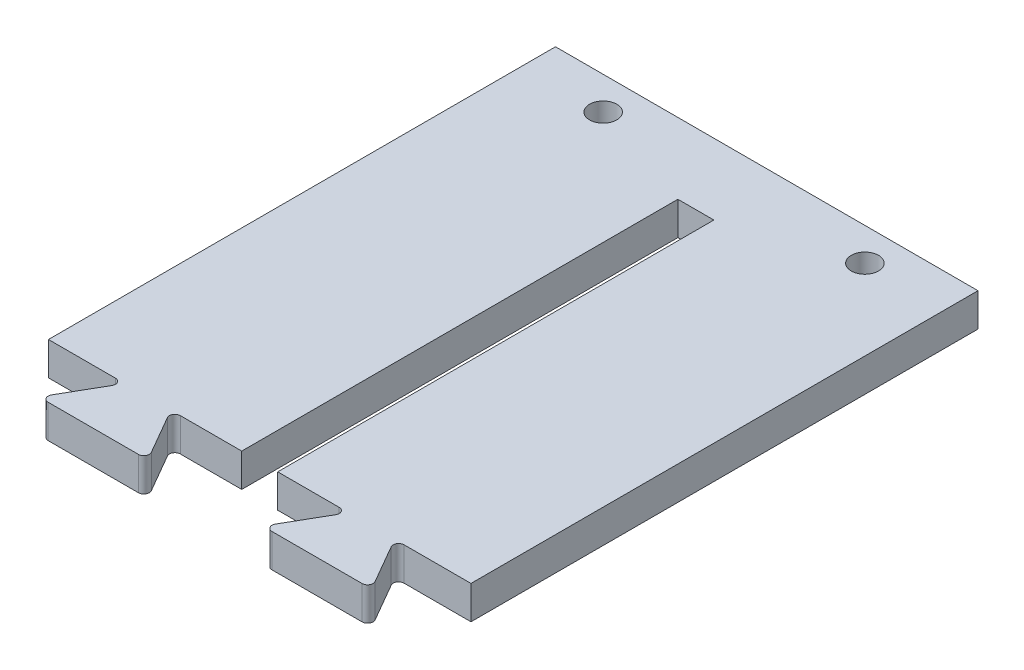
SolidWorks part; units mm, degrees
ref_plane "Front Plane" through (0, 0, 0) normal (0, 0, 1) x (1, 0, 0)
ref_plane "Top Plane" through (0, 0, 0) normal (0, 1, 0) x (1, 0, 0)
ref_plane "Right Plane" through (0, 0, 0) normal (1, 0, 0) x (0, 0, -1)
sketch "Sketch1" plane through (0, 0, 0) normal (0, 1, 0) x (1, 0, 0)
  line L0 (-19.375, 0) -> (-19.375, 46.5)
  line L1 (-19.375, 46.5) -> (19.375, 46.5)
  line L2 (19.375, 46.5) -> (19.375, 0)
  line L3 (19.375, 0) -> (12.375, 0)
  line L4 (12.375, 0) -> (15.2618, -5)
  line L5 (15.2618, -5) -> (5.2618, -5)
  line L6 (5.2618, -5) -> (8.1485, 0)
  line L7 (8.1485, 0) -> (-8.1485, 0)
  line L8 (-8.1485, 0) -> (-5.2618, -5)
  line L9 (-5.2618, -5) -> (-15.2618, -5)
  line L10 (-15.2618, -5) -> (-12.375, 0)
  line L11 (-12.375, 0) -> (-19.375, 0)
  point P13 (0, 0)
  dimension "D1" = 46.5
  dimension "D2" = 38.75
  dimension "D3" = 10
  dimension "D4" = 10
  dimension "D5" = 60
  dimension "D6" = 60
  dimension "D7" = 7
  dimension "D8" = 7
  dimension "D9" = 5
  dimension "D10" = 5
extrude "Boss-Extrude1" add sketch "Sketch1" along normal blind 3.05
fillet "Fillet1" radius 0.5 8 edges at (12.375, 1.525, 0) (15.2618, 1.525, 5) (5.2618, 1.525, 5) (8.1485, 1.525, 0) (-8.1485, 1.525, 0) (-5.2618, 1.525, 5) (-15.2618, 1.525, 5) (-12.375, 1.525, 0)
sketch "Sketch3" plane through (0, 3.05, 0) normal (0, 1, 0) x (1, 0, 0)
  line L0 (0, 40) -> (0, 0) construction
  line L2 (19.375, 46.5) -> (-19.375, 46.5) construction
  line L3 (-1.65, 40) -> (1.65, 40)
  line L4 (-1.65, 40) -> (-1.65, 0)
  line L5 (-1.65, 0) -> (1.65, 0)
  line L6 (1.65, 40) -> (1.65, 0)
  line L8 (-1.65, -1.2) -> (1.65, -1.2)
  line L9 (-1.65, -1.2) -> (-1.65, -2.2)
  line L10 (-1.65, -2.2) -> (1.65, -2.2)
  line L11 (1.65, -1.2) -> (1.65, -2.2)
  point P8 (0, 40)
  point P15 (0, -1.2)
  dimension "D1" = 3.3
  dimension "D2" = 40
  dimension "D3" = 6.5
  dimension "D4" = 1.2
  dimension "D5" = 1
extrude "Cut-Extrude2" cut sketch "Sketch3" against normal through all
sketch "Sketch8" plane through (0, 3.05, 0) normal (0, 1, 0) x (1, 0, 0)
  line L0 (0, 0) -> (0, 40) construction
  line L1 (-11.2618, 37) -> (-9.2618, 37)
  line L2 (-11.2618, 37) -> (-11.2618, 3)
  line L3 (-11.2618, 3) -> (-9.2618, 3)
  line L4 (-9.2618, 37) -> (-9.2618, 3)
  line L5 (-19.375, 0) -> (-13.241, 0) construction
  line L6 (-14.3957, -5) -> (-6.1278, -5) construction
  line L8 (11.2618, 3) -> (9.2618, 3)
  line L9 (9.2618, 37) -> (9.2618, 3)
  line L10 (11.2618, 37) -> (9.2618, 37)
  line L11 (11.2618, 37) -> (11.2618, 3)
  line L12 (1.65, 40) -> (-1.65, 40) construction
  point P5 (-10.2618, -5)
  point P10 (-10.2618, 3)
  dimension "D1" = 2
  dimension "D2" = 3
  dimension "D3" = 3
extrude "Cut-Extrude3" [suppressed] cut sketch "Sketch8" against normal through all
fillet "Fillet2" [suppressed] radius 0.5
sketch "Damper Hole Locations" plane through (0, 3.05, 0) normal (0, 1, 0) x (1, 0, 0)
  line L0 (0, 40) -> (0, 0) construction
  line L3 (19.375, 46.5) -> (-19.375, 46.5) construction
  circle A0 centre (-12, 43.5) radius 1.5
  circle A1 centre (12, 43.5) radius 1.5
  dimension "D1" = 3
  dimension "D2" = 12
  dimension "D3" = 3
hole_wizard "M3 Tapped Damper Holes" positions "Sketch6" profile "Sketch7" tap size "M3x0.5" standard "ANSI Metric" end condition through all
sketch "Sketch6" plane through (0, 3.05, 0) normal (0, 1, 0) x (1, 0, 0)
  point P0 (-12, 43.5)
  point P3 (12, 43.5)
sketch "Sketch7" plane through (-12, 3.05, -43.5) normal (1, 0, 0) x (0, 0, 1)
  line L0 (0, 0) -> (0, 3.05)
  line L1 (0, 3.05) -> (1.25, 3.05)
  line L2 (1.25, 3.05) -> (1.25, 0)
  line L5 (1.25, 0) -> (0, 0)
  line L11 (0, -6.35) -> (0, 107.95) construction
  dimension "Thru Tap Drill Dia." = 2.5
  dimension "Thru Tap Drill Depth" = 3.05
cosmetic thread "Hole Thread1" parameters "D2"=3
cosmetic thread "Hole Thread2" parameters "D2"=3
sketch "Sketch9" plane through (0, 3.05, 0) normal (0, 1, 0) x (1, 0, 0)
  line L0 (-19.375, 46.5) -> (-18.875, 46.5)
  line L1 (19.375, 46.5) -> (-19.375, 46.5) construction
  line L2 (-18.875, 46.5) -> (-18.875, 0)
  line L3 (-19.375, 0) -> (-13.241, 0) construction
  line L4 (-18.875, 0) -> (-19.375, 0)
  line L5 (-19.375, 0) -> (-19.375, 46.5)
  line L6 (19.375, 46.5) -> (18.875, 46.5)
  line L7 (18.875, 46.5) -> (18.875, 0)
  line L8 (13.241, 0) -> (19.375, 0) construction
  line L9 (18.875, 0) -> (19.375, 0)
  line L10 (19.375, 0) -> (19.375, 46.5)
  dimension "D1" = 0.5
  dimension "D2" = 0.5
extrude "Cut-Extrude4" [suppressed] cut sketch "Sketch9" against normal through all
